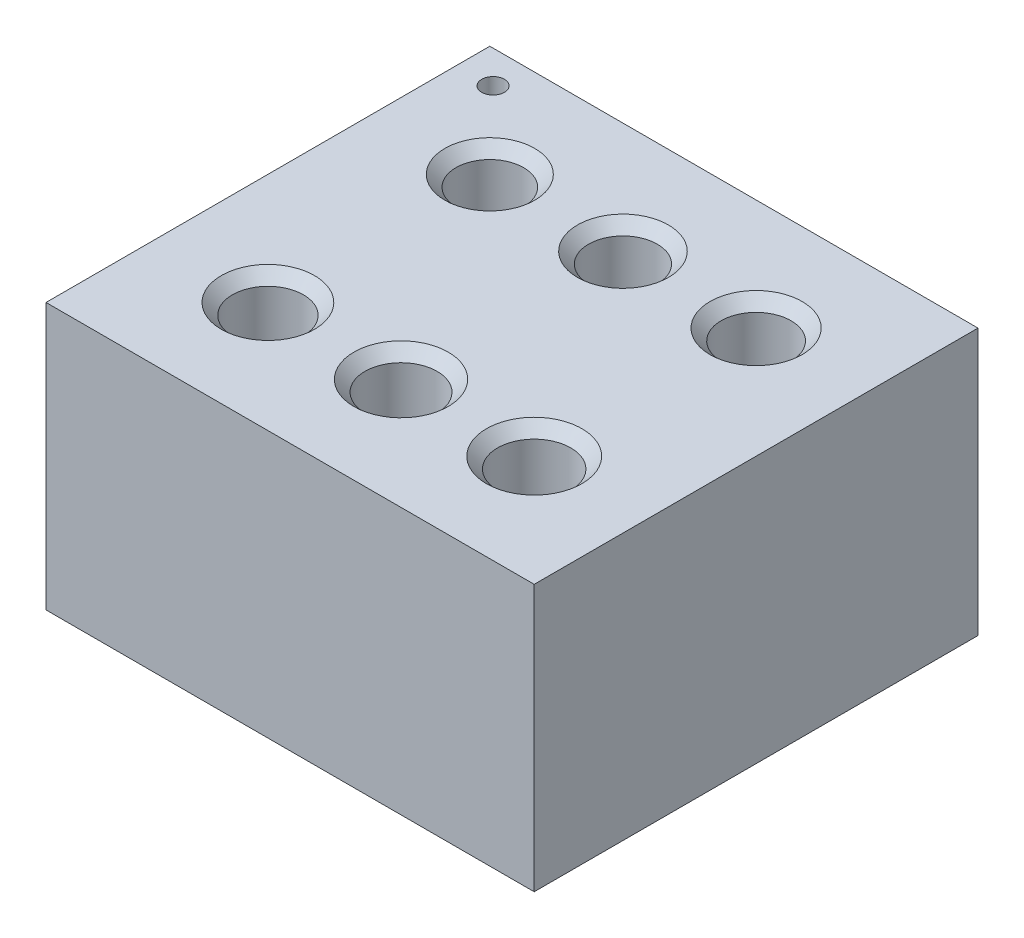
SolidWorks part; units mm, degrees
ref_plane "Front Plane" through (0, 0, 0) normal (0, 0, 1) x (1, 0, 0)
ref_plane "Top Plane" through (0, 0, 0) normal (0, 1, 0) x (1, 0, 0)
ref_plane "Right Plane" through (0, 0, 0) normal (1, 0, 0) x (0, 0, -1)
sketch "Sketch1" plane through (0, 0, 0) normal (0, 1, 0) x (1, 0, 0)
  line L1 (-11, -10) -> (11, -10)
  line L2 (-11, -10) -> (-11, 10)
  line L3 (-11, 10) -> (11, 10)
  line L4 (11, -10) -> (11, 10)
  line L5 (-11, -10) -> (11, 10) construction
  line L6 (-11, 10) -> (11, -10) construction
  circle A0 centre (-6, 5) radius 1.525
  circle A1 centre (0, 5) radius 1.55
  circle A2 centre (6, 5) radius 1.575
  circle A3 centre (-6, -5) radius 1.6
  circle A4 centre (0, -5) radius 1.625
  circle A5 centre (6, -5) radius 1.65
  circle A6 centre (-9.3816, 8.5287) radius 0.5112
  point P0 (0, 0)
  dimension "D1" = 3.05
  dimension "D2" = 3.1
  dimension "D3" = 3.15
  dimension "D4" = 3.2
  dimension "D5" = 3.25
  dimension "D6" = 3.3
  dimension "D7" = 20
  dimension "D8" = 22
  dimension "D9" = 5
  dimension "D10" = 5
  dimension "D11" = 5
  dimension "2.5" = 5
  dimension "D12" = 5
  dimension "D13" = 5
  dimension "5" = 5
  dimension "D15" = 5
  dimension "D16" = 5
extrude "Boss-Extrude1" add sketch "Sketch1" against normal blind 12 contours A3 | A0 | L1 L4 L3 L2 A5 A4 A3 A2 A1 A0 | A1 | A4 | A5 | A2 region at (0.0044, 0, -0.0108) region at (-6, 0, -5) region at (0, 0, -5) region at (6, 0, -5) region at (-6, 0, 5) region at (0, 0, 5) region at (6, 0, 5)
extrude "Cut-Extrude1" cut sketch "Sketch1<3>" against normal through all contours A0 | A3 | A1 | A4 | A5 | A2 region at (-6, 0, -5) region at (0, 0, -5) region at (6, 0, -5) region at (-6, 0, 5) region at (0, 0, 5) region at (6, 0, 5)
sketch "Sketch1<3>" plane through (0, 0, 0) normal (0, 1, 0) x (1, 0, 0) same geometry as "Sketch1"
chamfer "Chamfer1" distance 0.5 angle 45 6 edges at (-6, 0, 6.6) (0, 0, 6.625) (6, 0, 6.65) (6, 0, -3.425) (0, 0, -3.45) (-6, 0, -3.475)
